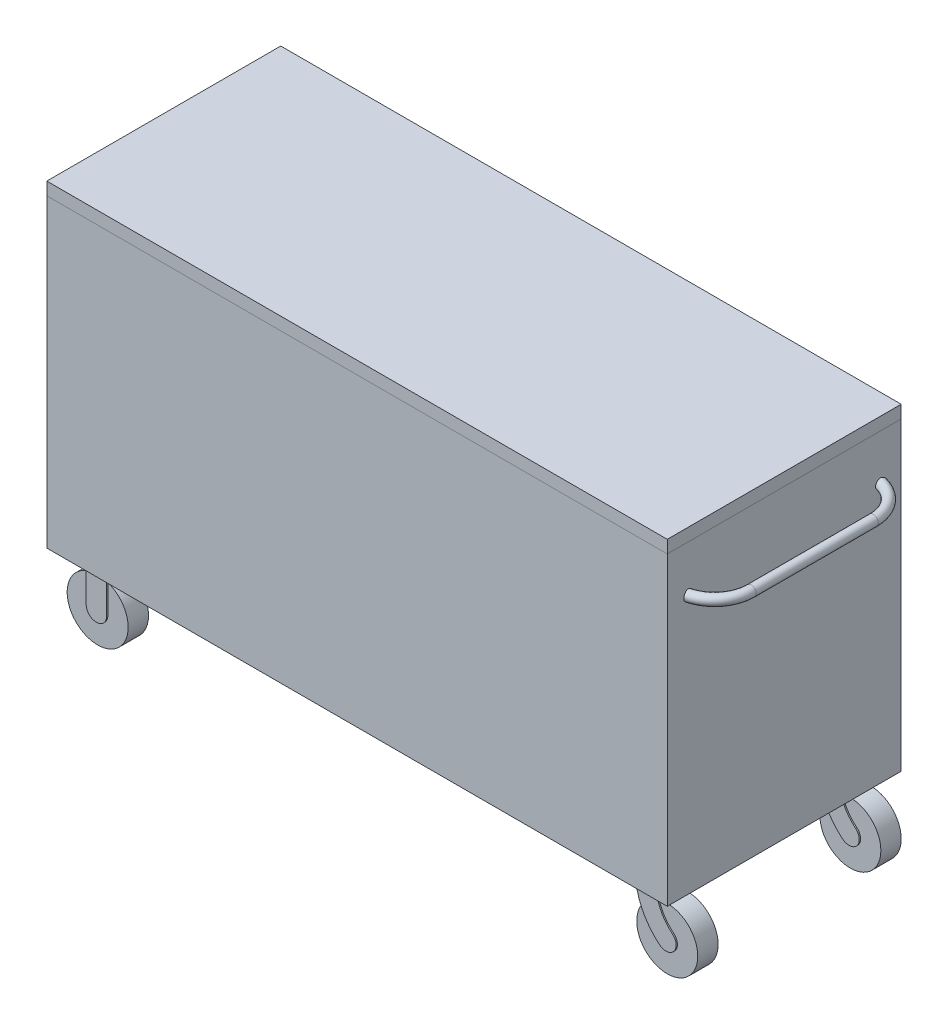
SolidWorks part; units mm, degrees
material "Plain Carbon Steel"
ref_plane "Front Plane" through (0, 0, 0) normal (0, 0, 1) x (1, 0, 0)
ref_plane "Top Plane" through (0, 0, 0) normal (0, 1, 0) x (1, 0, 0)
ref_plane "Right Plane" through (0, 0, 0) normal (1, 0, 0) x (0, 0, -1)
sketch "Sketch1" plane through (0, 0, 0) normal (0, 1, 0) x (1, 0, 0)
  line L1 (-774.7, -292.1) -> (774.7, -292.1)
  line L2 (-774.7, -292.1) -> (-774.7, 292.1)
  line L3 (-774.7, 292.1) -> (774.7, 292.1)
  line L4 (774.7, -292.1) -> (774.7, 292.1)
  line L5 (-774.7, -292.1) -> (774.7, 292.1) construction
  line L6 (-774.7, 292.1) -> (774.7, -292.1) construction
  point P0 (0, 0)
  dimension "D1" = 1549.4
  dimension "D2" = 584.2
extrude "Boss-Extrude1" add sketch "Sketch1" against normal blind 31.75
sketch "Sketch2" plane through (0, -31.75, 0) normal (0, -1, 0) x (1, 0, 0)
  line L4 (774.7, -292.1) -> (774.7, 292.1)
  line L5 (774.7, 292.1) -> (-774.7, 292.1)
  line L6 (-774.7, 292.1) -> (-774.7, -292.1)
  line L7 (-774.7, -292.1) -> (774.7, -292.1)
  line L8 (774.7, -292.1) -> (774.7, 292.1)
  line L9 (774.7, 292.1) -> (-774.7, 292.1)
  line L10 (-774.7, 292.1) -> (-774.7, -292.1)
  line L11 (-774.7, -292.1) -> (774.7, -292.1)
  dimension "D1" = 0
extrude "Boss-Extrude2" add sketch "Sketch2" along normal blind 762 separate body
ref_plane "Plane1" through (0, -146.05, 0) normal (0, 1, 0) x (1, 0, 0)
sketch "Sketch3" plane through (0, -146.05, 0) normal (0, 1, 0) x (1, 0, 0)
  line L0 (844.55, 152.4) -> (844.55, -152.4)
  line L1 (774.7, -292.1) -> (774.7, 292.1) construction
  line L2 (774.7, 292.1) -> (774.7, -292.1) construction
  arc A0 (844.55, -152.4) -> (774.7, -241.3) centre (753.0523, -152.4) cw
  arc A1 (844.55, 152.4) -> (774.7, 241.3) centre (753.0523, 152.4) ccw
  point P10 (844.55, 0)
  dimension "D1" = 69.85
  dimension "D2" = 482.6
  dimension "D3" = 304.8
sweep "Sweep1" add path "Sketch3" circular profile diameter 25.4 parameters "D3"=25.4
ref_plane "Plane2" through (0, 0, 228.6) normal (0, 0, 1) x (1, 0, 0)
sketch "Sketch13" plane through (0, 0, 228.6) normal (0, 0, 1) x (1, 0, 0)
  line L0 (774.7, -793.75) -> (774.7, -31.75) construction
  line L1 (-774.7, -793.75) -> (-774.7, -31.75) construction
  line L2 (-774.7, 0) -> (774.7, 0) construction
  circle A0 centre (736.6, -901.7) radius 76.2
  circle A1 centre (-685.8, -901.7) radius 76.2
  point P8 (736.6, -977.9)
  point P11 (0, 0)
  dimension "D3" = 152.4
  dimension "D1" = 38.1
  dimension "D2" = 88.9
  dimension "D4" = 977.9
extrude "Boss-Extrude3" add sketch "Sketch13" along normal mid plane 50.8 separate body
sketch "Sketch14" plane through (0, 0, 254) normal (0, 0, 1) x (1, 0, 0)
  line L0 (-711.2, -793.75) -> (-660.4, -793.75)
  line L1 (774.7, -793.75) -> (-774.7, -793.75) construction
  line L2 (-660.4, -793.75) -> (-660.4, -901.7)
  line L3 (-711.2, -901.7) -> (-711.2, -793.75)
  line L4 (660.4, -793.75) -> (711.2, -793.75)
  line L5 (-660.4, -793.75) -> (660.4, -793.75) construction
  arc A0 (-660.4, -901.7) -> (-711.2, -901.7) centre (-685.8, -901.7) cw
  arc A1 (711.2, -793.75) -> (752.7898, -882.1283) centre (825.8969, -793.75) ccw
  arc A2 (752.7898, -882.1283) -> (720.4102, -921.2717) centre (736.6, -901.7) cw
  arc A3 (720.4102, -921.2717) -> (660.4, -793.75) centre (825.8969, -793.75) cw
  circle A4 centre (736.6, -901.7) radius 76.2 construction
  circle A5 centre (-685.8, -901.7) radius 76.2 construction
  point P18 (0, -793.75)
  point P20 (750.7264, -880.5906)
  point P21 (727.2689, -925.324)
  dimension "D1" = 50.8
extrude "Boss-Extrude4" add sketch "Sketch14" along normal mid plane 6.35
mirror "Mirror1" about plane through (0, 0, 228.6) normal (0, 0, 1) of "Boss-Extrude4"
mirror "Mirror2" about plane through (0, 0, 0) normal (0, 0, 1) of bodies 108 109
